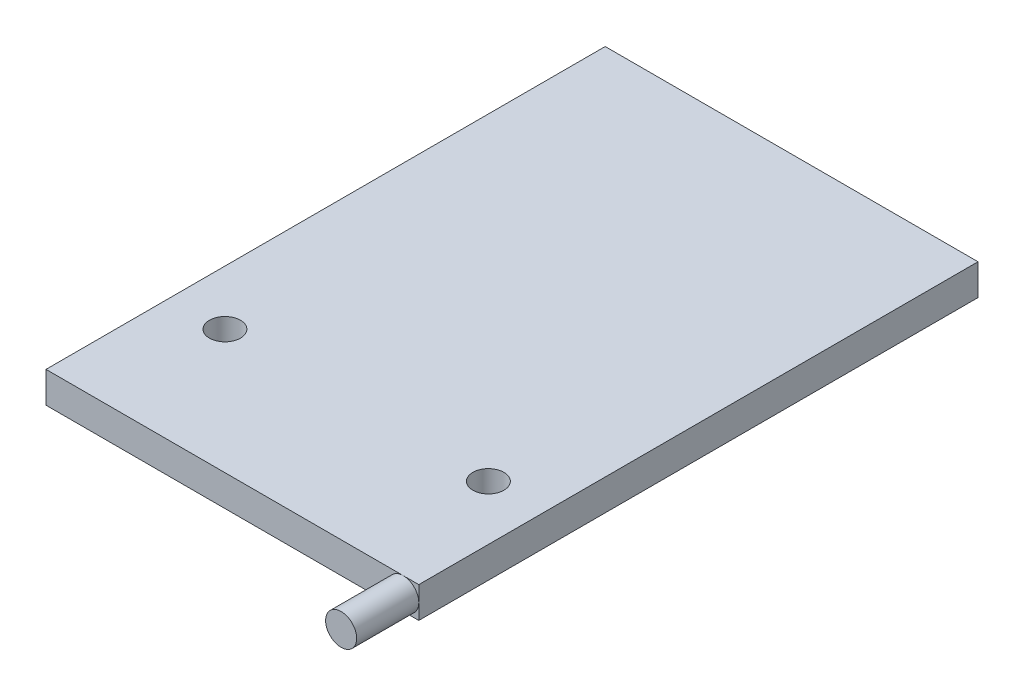
SolidWorks part; units mm, degrees
ref_plane "Front Plane" through (0, 0, 0) normal (0, 0, 1) x (1, 0, 0)
ref_plane "Top Plane" through (0, 0, 0) normal (0, 1, 0) x (1, 0, 0)
ref_plane "Right Plane" through (0, 0, 0) normal (1, 0, 0) x (0, 0, -1)
sketch "Sketch1" plane through (0, 0, 0) normal (0, 1, 0) x (1, 0, 0)
  line L0 (0, -20) -> (60, -20) construction
  line L2 (0, 0) -> (0, -40)
  line L3 (0, -40) -> (60, -40)
  line L4 (60, 0) -> (60, -40)
  line L5 (60, -20) -> (30, -40) construction
  line L6 (30, -40) -> (30, 0) construction
  line L9 (0, 0) -> (0, 50)
  line L10 (0, 50) -> (60, 50)
  line L11 (60, 0) -> (60, 50)
  circle A0 centre (51.2, -20) radius 2.5
  circle A1 centre (8.8, -20) radius 2.5
  dimension "D3" = 5
  dimension "D1" = 60
  dimension "D2" = 40
  dimension "D4" = 21.2
  dimension "D5" = 50
extrude "Boss-Extrude1" add sketch "Sketch1" along normal blind 5
sketch "Sketch3" plane through (0, 0, 40) normal (0, 0, 1) x (1, 0, 0)
  line L0 (60, 5) -> (60, 0) construction
  line L2 (0, 5) -> (60, 5) construction
  circle A0 centre (57.5, 2.5) radius 2.5
  dimension "D1" = 5
extrude "Boss-Extrude2" add sketch "Sketch3" along normal blind 10
